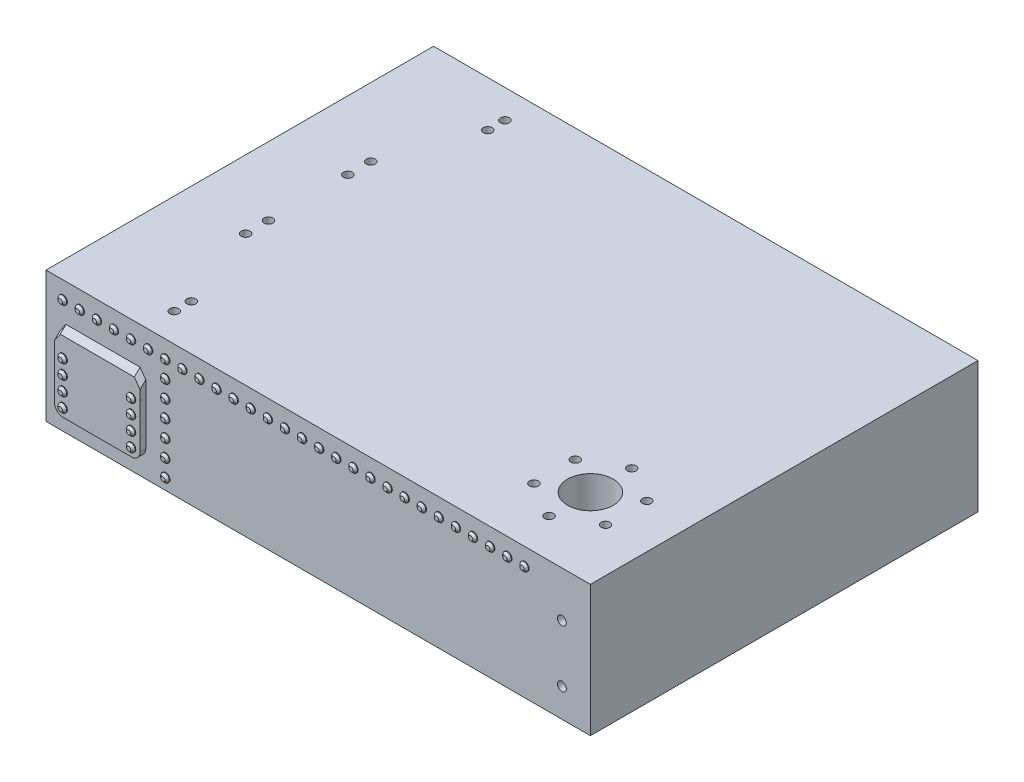
SolidWorks part; units mm, degrees
ref_plane "Front Plane" through (0, 0, 0) normal (0, 0, 1) x (1, 0, 0)
ref_plane "Top Plane" through (0, 0, 0) normal (0, 1, 0) x (1, 0, 0)
ref_plane "Right Plane" through (0, 0, 0) normal (1, 0, 0) x (0, 0, -1)
sketch "Sketch1" plane through (0, 0, 0) normal (0, 1, 0) x (1, 0, 0)
  line L1 (0, 0) -> (191, 0)
  line L2 (0, 0) -> (0, 136)
  line L3 (0, 136) -> (191, 136)
  line L4 (191, 0) -> (191, 136)
  dimension "D1" = 191
  dimension "D2" = 136
extrude "Boss-Extrude1" add sketch "Sketch1" along normal blind 46
sketch "Sketch3" plane through (0, 0, 0) normal (0, -1, 0) x (1, 0, 0)
  line L0 (0, -136) -> (0, 0) construction
  line L1 (5, -5) -> (186, -5)
  line L2 (5, -5) -> (5, -131)
  line L3 (5, -131) -> (186, -131)
  line L4 (186, -5) -> (186, -131)
  line L6 (191, -136) -> (0, -136) construction
  line L7 (191, 0) -> (191, -136) construction
  line L8 (0, 0) -> (191, 0) construction
  dimension "D1" = 5
  dimension "D2" = 5
  dimension "D3" = 5
  dimension "D4" = 5
extrude "Cut-Extrude1" cut sketch "Sketch3" against normal offset from surface (41 mm away) 5 contours L2 L3 L4 L1 up to face at (95.5, 46, -68)
ref_point "FrontLeft"
sketch "Sketch5" plane through (0, 0, -136) normal (0, 0, -1) x (-1, 0, 0)
  line L0 (-191, 46) -> (-119.5, 46)
  line L1 (-191, 46) -> (0, 46) construction
  line L2 (-119.5, 46) -> (-119.5, 0) construction
  line L3 (-191, 0) -> (0, 0) construction
  point P5 (-119.5, 23)
  dimension "D1" = 71.5
sketch "Sketch8" plane through (0, 0, 0) normal (0, 0, 1) x (1, 0, 0)
  line L1 (119.5, 46) -> (119.5, 0) construction
  line L2 (0, 46) -> (191, 46) construction
  line L3 (0, 0) -> (191, 0) construction
  point P0 (119.5, 23)
ref_point "SuspensionMountLeft"
ref_point "SuspensionMountRight"
sketch "Sketch9" plane through (0, 0, -136) normal (0, 0, -1) x (-1, 0, 0)
  line L0 (0, 46) -> (0, 0) construction
  line L1 (-5, 31) -> (-35, 31)
  line L2 (-5, 31) -> (-5, 6.2153)
  line L3 (-5, 6.2153) -> (-35, 6.2153)
  line L4 (-35, 31) -> (-35, 6.2153)
  line L5 (-191, 46) -> (0, 46) construction
  dimension "D1" = 5
  dimension "D2" = 15
  dimension "D3" = 30
extrude "Boss-Extrude2" add sketch "Sketch9" along normal blind 2
chamfer "Chamfer2" distance 2 angle 45 1 edges at (20, 31, -136)
fillet "Fillet1" radius 3 2 edges at (35, 6.2153, -137) (5, 6.2153, -137)
chamfer "Chamfer3" distance 2 angle 45 2 edges at (35, 32, -137) (5, 32, -137)
sketch "Sketch10" plane through (0, 0, 0) normal (0, 0, 1) x (1, 0, 0)
  line L4 (35, 31) -> (5, 31)
  line L5 (35, 6.2153) -> (35, 31)
  line L6 (5, 6.2153) -> (35, 6.2153)
  line L7 (5, 31) -> (5, 6.2153)
  line L8 (35, 31) -> (5, 31)
  line L9 (35, 6.2153) -> (35, 31)
  line L10 (5, 6.2153) -> (35, 6.2153)
  line L11 (5, 31) -> (5, 6.2153)
  dimension "D1" = 0
extrude "Boss-Extrude3" add sketch "Sketch10" along normal blind 2
chamfer "Chamfer4" distance 2 angle 45 1 edges at (20, 31, 0)
fillet "Fillet2" radius 3 2 edges at (35, 6.2153, 1) (5, 6.2153, 1)
chamfer "Chamfer5" distance 2 angle 45 2 edges at (35, 32, 1) (5, 32, 1)
sketch "Sketch23" plane through (0, 0, 2) normal (0, 0, 1) x (1, 0, 0)
  line L0 (8, 9.2153) -> (8, 31) construction
  line L1 (33, 31) -> (7, 31) construction
  line L2 (32, 9.2153) -> (32, 31) construction
  circle A0 centre (8, 9.2153) radius 1.5
  circle A1 centre (32, 9.2153) radius 1.5
  circle A2 centre (8, 14.2153) radius 1.5
  circle A3 centre (32, 14.2153) radius 1.5
  circle A4 centre (8, 19.2153) radius 1.5
  circle A5 centre (32, 19.2153) radius 1.5
  circle A6 centre (8, 24.2153) radius 1.5
  circle A7 centre (32, 24.2153) radius 1.5
  dimension "D1" = 3
  dimension "D2" = 3
  dimension "D3" = 4
extrude "Boss-Extrude8" add sketch "Sketch23" along normal blind 1 contours A4 | A2 | A0 | A1 | A3 | A5 | A7 | A6 region at (8, 9.2153, 2) region at (32, 9.2153, 2) region at (8, 14.2153, 2) region at (32, 14.2153, 2) region at (8, 19.2153, 2) region at (32, 19.2153, 2) region at (32, 24.2153, 2)
chamfer "Chamfer11" distance 0.75 angle 45 8 edges at (9.5, 24.2153, 3) (33.5, 9.2153, 3) (33.5, 14.2153, 3) (33.5, 19.2153, 3) (33.5, 24.2153, 3) (9.5, 9.2153, 3) (9.5, 14.2153, 3) (9.5, 19.2153, 3)
ref_plane "Plane1" through (0, 0, -68) normal (0, 0, 1) x (1, 0, 0)
mirror "Mirror1" about plane through (0, 0, -68) normal (0, 0, 1) of "Chamfer11", "Boss-Extrude8"
sketch "Sketch18" plane through (0, 41, 0) normal (0, -1, 0) x (1, 0, 0)
  line L25 (77.9594, -66) -> (76.1297, -62.8309)
  line L26 (76.1297, -62.8309) -> (72.4703, -62.8309)
  line L27 (72.4703, -62.8309) -> (70.6406, -66)
  line L28 (70.6406, -66) -> (72.4703, -69.1691)
  line L29 (72.4703, -69.1691) -> (76.1297, -69.1691)
  line L30 (76.1297, -69.1691) -> (77.9594, -66)
  line L31 (178.5415, -60.5) -> (176.5207, -57)
  line L32 (176.5207, -57) -> (172.4793, -57)
  line L33 (172.4793, -57) -> (170.4585, -60.5)
  line L34 (170.4585, -60.5) -> (172.4793, -64)
  line L35 (172.4793, -64) -> (176.5207, -64)
  line L36 (176.5207, -64) -> (178.5415, -60.5)
  line L37 (78.3415, -114) -> (76.3207, -110.5)
  line L38 (76.3207, -110.5) -> (72.2793, -110.5)
  line L39 (72.2793, -110.5) -> (70.2585, -114)
  line L40 (70.2585, -114) -> (72.2793, -117.5)
  line L41 (72.2793, -117.5) -> (76.3207, -117.5)
  line L42 (76.3207, -117.5) -> (78.3415, -114)
  line L43 (178.5415, -113) -> (176.5207, -109.5)
  line L44 (176.5207, -109.5) -> (172.4793, -109.5)
  line L45 (172.4793, -109.5) -> (170.4585, -113)
  line L46 (170.4585, -113) -> (172.4793, -116.5)
  line L47 (172.4793, -116.5) -> (176.5207, -116.5)
  line L48 (176.5207, -116.5) -> (178.5415, -113)
  circle A1 centre (74.3, -66) radius 3.1691 construction
  circle A2 centre (174.5, -60.5) radius 1.5
  circle A3 centre (174.5, -60.5) radius 1.5
  circle A4 centre (174.5, -113) radius 1.5
  circle A5 centre (174.5, -113) radius 1.5
  circle A6 centre (74.3, -114) radius 1.5
  circle A7 centre (74.3, -114) radius 1.5
  circle A8 centre (74.3, -66) radius 1.5
  circle A12 centre (74.3, -66) radius 1.5
  circle A13 centre (174.5, -60.5) radius 3.5 construction
  circle A14 centre (74.3, -114) radius 3.5 construction
  circle A15 centre (174.5, -113) radius 3.5 construction
  dimension "D1" = 0
  dimension "D2" = 0
  dimension "D3" = 0
  dimension "D4" = 0
extrude "Boss-Extrude7" add sketch "Sketch18" along normal blind 14 contours L29 L30 L25 L26 L27 L28 A12 | A12 | L41 L42 L37 L38 L39 L40 A7 | A7 | L47 L48 L43 L44 L45 L46 A5 | A5 | L35 L36 L31 L32 L33 L34 A3 | A3 region at (76.9607, 41, -67.5361) region at (177.4385, 41, -62.1965) region at (77.2385, 41, -115.6965) region at (177.4385, 41, -114.6965) region at (174.5, 41, -60.5) region at (174.5, 41, -113) region at (74.3, 41, -114) region at (74.3, 41, -66)
sketch "Sketch22" plane through (0, 0, 0) normal (-1, 0, 0) x (0, 0, 1)
  line L0 (0, 46) -> (0, 0) construction
  line L1 (-10, 10) -> (-80, 10)
  line L2 (-10, 10) -> (-10, 38)
  line L3 (-10, 38) -> (-80, 38)
  line L4 (-80, 10) -> (-80, 38)
  line L5 (-136, 0) -> (0, 0) construction
  line L6 (-136, 46) -> (0, 46) construction
  dimension "D1" = 10
  dimension "D2" = 10
  dimension "D3" = 8
  dimension "D4" = 70
extrude "Cut-Extrude2" [suppressed] cut sketch "Sketch22" against normal up to next
chamfer "Chamfer10" [suppressed] distance 28 angle 45
fillet "Fillet3" [suppressed] radius 3
sketch "Sketch24" plane through (0, 0, 0) normal (0, 0, 1) x (1, 0, 0)
  line L0 (0, 40) -> (191, 40) construction
  line L1 (0, 46) -> (0, 0) construction
  line L2 (191, 46) -> (191, 0) construction
  line L3 (0, 46) -> (191, 46) construction
  circle A0 centre (6, 40) radius 1.5
  circle A1 centre (12, 40) radius 1.5
  circle A2 centre (18, 40) radius 1.5
  circle A3 centre (24, 40) radius 1.5
  circle A4 centre (30, 40) radius 1.5
  circle A5 centre (36, 40) radius 1.5
  circle A6 centre (42, 40) radius 1.5
  circle A7 centre (48, 40) radius 1.5
  circle A8 centre (54, 40) radius 1.5
  circle A9 centre (60, 40) radius 1.5
  circle A10 centre (66, 40) radius 1.5
  circle A11 centre (72, 40) radius 1.5
  circle A12 centre (78, 40) radius 1.5
  circle A13 centre (84, 40) radius 1.5
  circle A14 centre (90, 40) radius 1.5
  circle A15 centre (96, 40) radius 1.5
  circle A16 centre (102, 40) radius 1.5
  circle A17 centre (108, 40) radius 1.5
  circle A18 centre (114, 40) radius 1.5
  circle A19 centre (120, 40) radius 1.5
  circle A20 centre (126, 40) radius 1.5
  circle A21 centre (132, 40) radius 1.5
  circle A22 centre (138, 40) radius 1.5
  circle A23 centre (144, 40) radius 1.5
  circle A24 centre (150, 40) radius 1.5
  circle A25 centre (156, 40) radius 1.5
  circle A26 centre (162, 40) radius 1.5
  circle A27 centre (168, 40) radius 1.5
  circle A28 centre (42, 34) radius 1.5
  circle A29 centre (42, 28) radius 1.5
  circle A30 centre (42, 22) radius 1.5
  circle A31 centre (42, 16) radius 1.5
  circle A32 centre (42, 10) radius 1.5
  circle A33 centre (42, 4) radius 1.5
  dimension "D2" = 3
  dimension "D1" = 6
  dimension "D3" = 6
  dimension "D4" = 28
  dimension "D5" = 7
extrude "Boss-Extrude9" add sketch "Sketch24" along normal blind 1
chamfer "Chamfer12" distance 0.75 angle 45 34 edges at (169.5, 40, 1) (163.5, 40, 1) (157.5, 40, 1) (151.5, 40, 1) (145.5, 40, 1) (139.5, 40, 1) (133.5, 40, 1) (127.5, 40, 1) (121.5, 40, 1) (115.5, 40, 1) (109.5, 40, 1) (103.5, 40, 1) (97.5, 40, 1) (91.5, 40, 1) (85.5, 40, 1) (79.5, 40, 1) (73.5, 40, 1) (67.5, 40, 1) (43.5, 4, 1) (43.5, 10, 1) (43.5, 16, 1) (43.5, 22, 1) (43.5, 28, 1) (43.5, 34, 1) (61.5, 40, 1) (55.5, 40, 1) (49.5, 40, 1) (43.5, 40, 1) (37.5, 40, 1) (31.5, 40, 1) (25.5, 40, 1) (19.5, 40, 1) (13.5, 40, 1) (7.5, 40, 1)
mirror "Mirror3" about plane through (0, 0, -68) normal (0, 0, 1) of "Chamfer12", "Boss-Extrude9"
sketch "Sketch25" plane through (0, 0, -131) normal (0, 0, 1) x (1, 0, 0)
  circle A0 centre (181, 30) radius 1.55 construction
  circle A1 centre (181, 10) radius 1.55 construction
  circle A2 centre (181, 30) radius 1.55
  circle A3 centre (181, 10) radius 1.55
extrude "Cut-Extrude3" cut sketch "Sketch25" against normal through all
sketch "Sketch26" plane through (0, 0, -5) normal (0, 0, -1) x (-1, 0, 0)
  circle A1 centre (-181, 10) radius 1.55
  circle A2 centre (-181, 10) radius 1.55
  circle A3 centre (-181, 30) radius 1.55
  circle A4 centre (-181, 30) radius 1.55
  dimension "D1" = 0
  dimension "D2" = 0
extrude "Cut-Extrude4" cut sketch "Sketch26" against normal through all
sketch "Sketch27" plane through (0, 46, 0) normal (0, 1, 0) x (1, 0, 0)
  line L0 (191, 0) -> (191, 136) construction
  line L1 (0, 0) -> (191, 0) construction
  circle A0 centre (163, 28) radius 1
  dimension "D1" = 2
  dimension "D2" = 28
  dimension "D3" = 28
sketch "Sketch28" plane through (0, 41, 0) normal (0, -1, 0) x (1, 0, 0)
  circle A0 centre (163, -13.5) radius 1.55 construction
  circle A1 centre (163, -28) radius 18
  circle A2 centre (163, -28) radius 18
  circle A3 centre (163, -28) radius 8
  circle A4 centre (163, -28) radius 8
  circle A5 centre (175.5574, -20.75) radius 1.55 construction
  circle A6 centre (175.5574, -35.25) radius 1.55 construction
  circle A7 centre (163, -42.5) radius 1.55 construction
  circle A8 centre (150.4426, -35.25) radius 1.55 construction
  circle A9 centre (150.4426, -20.75) radius 1.55 construction
  circle A10 centre (163, -13.5) radius 1.55
  circle A11 centre (175.5574, -20.75) radius 1.55
  circle A12 centre (175.5574, -35.25) radius 1.55
  circle A13 centre (163, -42.5) radius 1.55
  circle A14 centre (150.4426, -35.25) radius 1.55
  circle A15 centre (150.4426, -20.75) radius 1.55
  circle A17 centre (163, -28) radius 11
  circle A18 centre (163, -28) radius 11
  dimension "D1" = 0
  dimension "D2" = 0
  dimension "D3" = 0
extrude "Cut-Extrude5" cut sketch "Sketch28" against normal through all contours A13 | A12 | A11 | A10 | A15 | A14 region at (163, 41, -13.5) region at (175.5574, 41, -20.75) region at (175.5574, 41, -35.25) region at (163, 41, -42.5) region at (150.4426, 41, -35.25) region at (150.4426, 41, -20.75)
extrude "Cut-Extrude6" cut sketch "Sketch28<3>" against normal through all contours A4 region at (163, 41, -28)
sketch "Sketch28<3>" plane through (0, 41, 0) normal (0, -1, 0) x (1, 0, 0) same geometry as "Sketch28"
extrude "Boss-Extrude10" add sketch "Sketch28<4>" along normal blind 40 contours A18 A4 region at (152.3111, 41, -28)
sketch "Sketch28<4>" plane through (0, 41, 0) normal (0, -1, 0) x (1, 0, 0) same geometry as "Sketch28"
sketch "Sketch29" plane through (0, 1, 0) normal (0, -1, 0) x (1, 0, 0)
  line L0 (163, -28) -> (163, -43.0058) construction
  line L1 (163, -43.0058) -> (162, -43.0058)
  line L2 (163, -43.0058) -> (164, -43.0058)
  line L3 (164, -43.0058) -> (164, -13.0058)
  line L4 (164, -13.0058) -> (162, -13.0058)
  line L5 (162, -13.0058) -> (162, -43.0058)
  dimension "D2" = 1
  dimension "D1" = 1
  dimension "D3" = 30
extrude "Cut-Extrude7" cut sketch "Sketch29" against normal blind 20
ref_plane "Plane2" through (163, 46, -28) normal (0, 0, 1) x (1, 0, 0)
sketch "Sketch30" plane through (163, 46, -28) normal (0, 0, 1) x (1, 0, 0)
  line L0 (11, -5) -> (11, -46) construction
  line L1 (11, -45) -> (11, -5) construction
  line L2 (18, -5) -> (18, -46) construction
  line L3 (18, -5) -> (11, -25.5) construction
  line L4 (23, -5) -> (-158, -5)
  line L5 (-158, -5) -> (-158, -46)
  line L6 (-158, -46) -> (23, -46)
  line L7 (23, -46) -> (23, -5)
  line L8 (23, -5) -> (-158, -5)
  line L9 (-158, -5) -> (-158, -46)
  line L10 (-158, -46) -> (23, -46)
  line L11 (23, -46) -> (23, -5)
  line L12 (17, -7.9286) -> (12, -22.5714)
  line L13 (17, -7.9286) -> (17, -5)
  line L14 (17, -5) -> (17, -4.9)
  line L15 (12, -22.5714) -> (11, -22.5714)
  line L16 (11, -22.5714) -> (10.9, -22.5714)
  line L17 (10.9, -22.5714) -> (10.9, -4.9)
  line L18 (10.9, -4.9) -> (17, -4.9)
  dimension "D2" = 1
  dimension "D3" = 1
  dimension "D4" = 0.1
  dimension "D5" = 0.1
  dimension "D1" = 0
extrude "Boss-Extrude11" add sketch "Sketch30" along normal mid plane 3 contours L17 L16 L15 L12 L13 L8 region at (176.2325, 34.2396, -28)
ref_axis "Axis1" through (163, 46, -28) along (0, -1, 0)
pattern_circular "CirPattern1" count 6 over 360 about axis through (163, 46, -28) along (0, -1, 0) of "Boss-Extrude11"
chamfer "Chamfer13" distance 0.5 angle 45 2 edges at (174, 1, -28) (152, 1, -28)
sketch "Sketch31" plane through (0, 41, 0) normal (0, -1, 0) x (1, 0, 0)
  circle A0 centre (35, -16) radius 1.55 construction
  circle A1 centre (35, -10) radius 1.55 construction
  circle A2 centre (35, -126) radius 1.55 construction
  circle A3 centre (35, -120) radius 1.55 construction
  circle A4 centre (35, -16) radius 1.55
  circle A5 centre (35, -10) radius 1.55
  circle A6 centre (35, -126) radius 1.55
  circle A7 centre (35, -120) radius 1.55
extrude "Cut-Extrude8" cut sketch "Sketch31" against normal up to next
sketch "Sketch32" plane through (5, 0, 0) normal (1, 0, 0) x (0, 0, -1)
  circle A0 centre (125.5, 17.25) radius 1.55 construction
  circle A1 centre (10.5, 17.25) radius 1.55 construction
  circle A2 centre (125.5, 17.25) radius 1.55
  circle A3 centre (10.5, 17.25) radius 1.55
extrude "Cut-Extrude9" cut sketch "Sketch32" against normal up to next
sketch "Sketch34" plane through (5, 0, 0) normal (1, 0, 0) x (0, 0, -1)
  circle A0 centre (46.0692, 8) radius 1.55 construction
  circle A1 centre (89.9308, 8) radius 1.55 construction
  circle A2 centre (46.0692, 8) radius 1.55
  circle A3 centre (89.9308, 8) radius 1.55
extrude "Cut-Extrude10" cut sketch "Sketch34" against normal up to next
sketch "Sketch35" plane through (0, 41, 0) normal (0, -1, 0) x (1, 0, 0)
  circle A0 centre (24, -46.0692) radius 1.55 construction
  circle A1 centre (24, -54.0692) radius 1.55 construction
  circle A2 centre (24, -81.9308) radius 1.55 construction
  circle A3 centre (24, -89.9308) radius 1.55 construction
  circle A4 centre (24, -46.0692) radius 1.55
  circle A5 centre (24, -54.0692) radius 1.55
  circle A6 centre (24, -81.9308) radius 1.55
  circle A7 centre (24, -89.9308) radius 1.55
extrude "Cut-Extrude11" cut sketch "Sketch35" against normal up to next
sketch "Sketch36" plane through (0, 46, 0) normal (0, 1, 0) x (1, 0, 0)
  line L0 (191, 68) -> (85, 68) construction
  line L1 (191, 0) -> (191, 136) construction
  dimension "D1" = 106
sketch "Sketch37" plane through (0, 0, 0) normal (0, -1, 0) x (1, 0, 0)
  line L4 (0, -136) -> (142.2, -136)
  line L5 (0, 0) -> (0, -136)
  line L6 (142.2, 0) -> (0, 0)
  line L7 (142.2, -136) -> (142.2, 0)
  line L8 (0, -136) -> (142.2, -136)
  line L9 (0, 0) -> (0, -136)
  line L10 (142.2, 0) -> (0, 0)
  line L11 (142.2, -136) -> (142.2, 0)
  arc A0 (8, -131) -> (5, -128) centre (5, -131) ccw construction
  arc A1 (5, -8) -> (8, -5) centre (5, -5) ccw construction
  arc A2 (134.2, -5) -> (137.2, -8) centre (137.2, -5) ccw construction
  arc A3 (137.2, -128) -> (134.2, -131) centre (137.2, -131) ccw construction
  arc A4 (8, -131) -> (5, -128) centre (5, -131) ccw
  arc A5 (5, -8) -> (8, -5) centre (5, -5) ccw
  arc A6 (134.2, -5) -> (137.2, -8) centre (137.2, -5) ccw
  arc A7 (137.2, -128) -> (134.2, -131) centre (137.2, -131) ccw
  circle A8 centre (5, -131) radius 3
  circle A9 centre (5, -5) radius 3
  circle A10 centre (137.2, -5) radius 3
  circle A11 centre (137.2, -131) radius 3
  line M9 (5, -131) -> (5, -5)
  line M10 (5, -5) -> (186, -5)
  line M12 (186, -131) -> (5, -131)
  dimension "D1" = 0
extrude "Boss-Extrude12" add sketch "Sketch37" against normal blind 12 contours A11 A7 M12 | A6 A10 M10 | A5 M9 M10 | A4 M12 M9 region at (137.2, 0, -129.7268) region at (137.2, 0, -6.2732) region at (6.2732, 0, -129.7268) region at (6.2732, 0, -6.2732)
chamfer "Chamfer14" distance 2.999 angle 45 4 edges at (7.1213, 12, -128.8787) (137.2, 12, -128) (137.2, 12, -8) (7.1213, 12, -7.1213)
sketch "Sketch38" plane through (0, 0, 0) normal (0, -1, 0) x (1, 0, 0)
  circle A0 centre (137.2, -131) radius 1.55
  circle A1 centre (137.2, -5) radius 1.55
  circle A2 centre (5, -5) radius 1.55
  circle A3 centre (5, -131) radius 1.55
  dimension "D1" = 3.1
  dimension "D2" = 3.1
  dimension "D3" = 3.1
  dimension "D4" = 3.1
extrude "Cut-Extrude12" cut sketch "Sketch38" against normal blind 2
sketch "Sketch39" plane through (0, 27, 0) normal (0, -1, 0) x (1, 0, 0)
  point P0 (74.3, -66)
  point P1 (74.3, -114)
  point P2 (174.5, -113)
  point P3 (174.5, -60.5)
hole_wizard "Ø2.0mm Dowel Hole1" positions "Sketch41" profile "Sketch42" hole size "Ø2.0" standard "ANSI Metric"
sketch "Sketch41" plane through (0, 27, 0) normal (0, -1, 0) x (-1, 0, 0)
  point P0 (-74.3, 66)
  point P3 (-74.3, 114)
  point P6 (-174.5, 113)
  point P9 (-174.5, 60.5)
sketch "Sketch42" plane through (74.3, 27, -66) normal (1, 0, 0) x (0, 0, -1)
  line L0 (0, 0) -> (0, 12.6009)
  line L1 (0, 12.6009) -> (1, 12)
  line L2 (1, 12) -> (1, 0)
  line L5 (1, 0) -> (0, 0)
  line L10 (0, 12.6009) -> (-1, 12) construction
  line L11 (0, -6.35) -> (0, 107.95) construction
  dimension "Hole Dia." = 2
  dimension "Hole Depth" = 12
  dimension "Drill Angle" = 118
